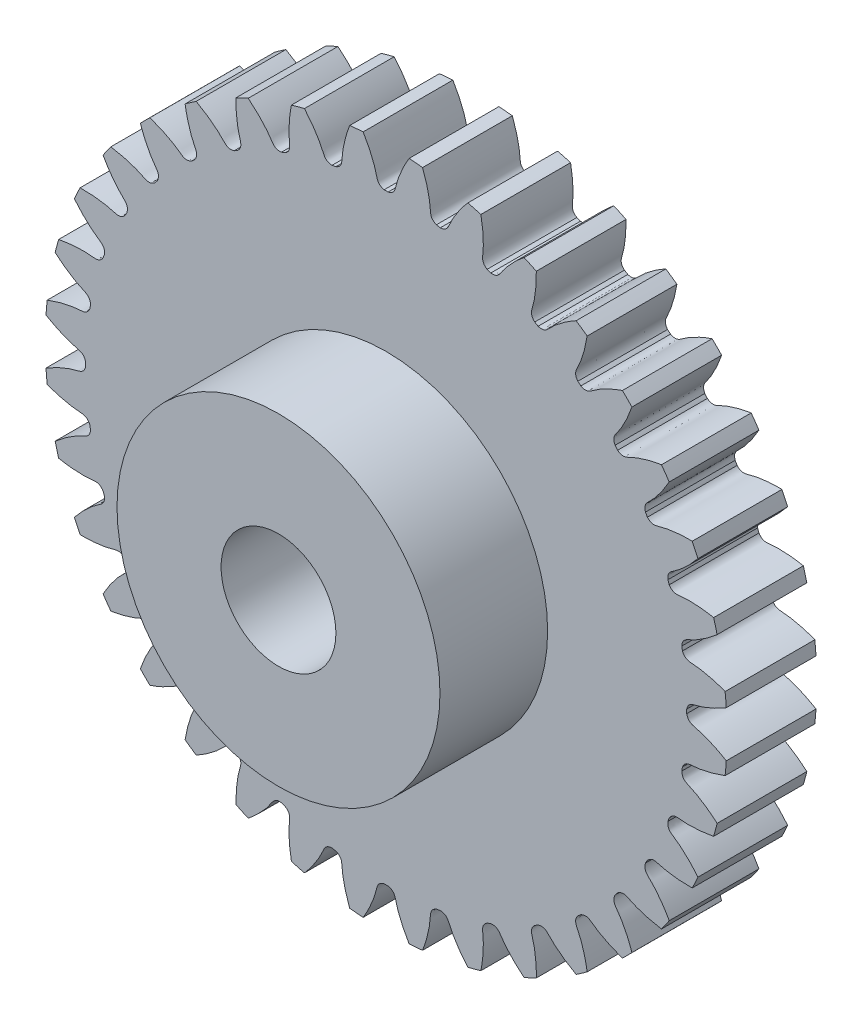
SolidWorks part; units mm, degrees
ref_plane "前视基准面" through (0, 0, 0) normal (0, 0, 1) x (1, 0, 0)
ref_plane "上视基准面" through (0, 0, 0) normal (0, 1, 0) x (1, 0, 0)
ref_plane "右视基准面" through (0, 0, 0) normal (1, 0, 0) x (0, 0, -1)
other "Configuration Table"
sketch "草图1" plane through (0, 0, 0) normal (0, 0, 1) x (1, 0, 0)
  circle A0 centre (0, 0) radius 9.5
extrude "凸台-拉伸1" add sketch "草图1" along normal blind 2.5
ref_axis "基准轴1" through (0, 0, 2.5) along (0, 0, -1)
sketch "草图2" plane through (0, 0, 0) normal (0, 0, 1) x (1, 0, 0)
  line L0 (0, 0) -> (0, 9.5) construction
  circle A0 centre (0, 0) radius 9.5 construction
  arc A1 (0.0549, 8.3748) -> (-0.0549, 8.3748) centre (0, 0) ccw
  arc A2 (1.757, 10.7884) -> (-1.757, 10.7884) centre (0, 0) ccw
  spline S0 degree 3 poles (0.0549, 8.3748) (0.235, 8.4152) (0.2505, 8.5493) (0.2882, 8.6914) (0.2997, 8.7319) (0.3131, 8.7753) (0.3284, 8.8217) (0.3457, 8.871) (0.3652, 8.9231) (0.3869, 8.9779) (0.4111, 9.0354) (0.4378, 9.0956) (0.4671, 9.1582) (0.4992, 9.2232) (0.5341, 9.2907) (0.5719, 9.3603) (0.6128, 9.4322) (0.6569, 9.5061) (0.7043, 9.582) (0.755, 9.6598) (0.8091, 9.7393) (0.8668, 9.8205) (0.9281, 9.9032) (0.9931, 9.9874) (1.0619, 10.0729) (1.1346, 10.1596) (1.2112, 10.2474) (1.2919, 10.3361) (1.3766, 10.4256) (1.4655, 10.5159) (1.5912, 10.6386) (1.6895, 10.7288) (1.757, 10.7884) knots 0 0 0 0 0.120371 0.133303 0.147364 0.162556 0.178878 0.19633 0.214913 0.234626 0.255469 0.277443 0.300547 0.324782 0.350146 0.376641 0.404267 0.433023 0.462909 0.493925 0.526072 0.559349 0.593757 0.629294 0.665963 0.703761 0.74269 0.782749 0.823939 0.866258 0.909709 1 1 1 1
  spline S1 degree 3 poles (-0.0549, 8.3748) (-0.235, 8.4152) (-0.2505, 8.5493) (-0.2882, 8.6914) (-0.2997, 8.7319) (-0.3131, 8.7753) (-0.3284, 8.8217) (-0.3457, 8.871) (-0.3652, 8.9231) (-0.3869, 8.9779) (-0.4111, 9.0354) (-0.4378, 9.0956) (-0.4671, 9.1582) (-0.4992, 9.2232) (-0.5341, 9.2907) (-0.5719, 9.3603) (-0.6128, 9.4322) (-0.6569, 9.5061) (-0.7043, 9.582) (-0.755, 9.6598) (-0.8091, 9.7393) (-0.8668, 9.8205) (-0.9281, 9.9032) (-0.9931, 9.9874) (-1.0619, 10.0729) (-1.1346, 10.1596) (-1.2112, 10.2474) (-1.2919, 10.3361) (-1.3766, 10.4256) (-1.4655, 10.5159) (-1.5912, 10.6386) (-1.6895, 10.7288) (-1.757, 10.7884) knots 0 0 0 0 0.120371 0.133303 0.147364 0.162556 0.178878 0.19633 0.214913 0.234626 0.255469 0.277443 0.300547 0.324782 0.350146 0.376641 0.404267 0.433023 0.462909 0.493925 0.526072 0.559349 0.593757 0.629294 0.665963 0.703761 0.74269 0.782749 0.823939 0.866258 0.909709 1 1 1 1
extrude "切除-拉伸1" cut sketch "草图2" along normal through all
pattern_circular "阵列(圆周)1" count 36 every 10 about axis through (0, 0, 2.5) along (0, 0, -1) of "切除-拉伸1"
sketch "草图3" plane through (0, 0, 0) normal (0, 0, 1) x (1, 0, 0)
  circle A0 centre (0, 0) radius 9 construction
  dimension "Dn" = 18
sketch "草图4" plane through (0, 0, 0) normal (0, 0, -1) x (-1, 0, 0)
  circle A0 centre (0, 0) radius 4.5
  dimension "D1" = 9
extrude "凸台-拉伸2" add sketch "草图4" against normal offset from surface (5.5 mm away) 3 up to face at (0, 0, 2.5) offset beyond the face yes
sketch "草图5" plane through (0, 0, 5.5) normal (0, 0, 1) x (1, 0, 0)
  circle A0 centre (0, 0) radius 1.6
  dimension "D1" = 3.2
extrude "切除-拉伸2" cut sketch "草图5" against normal up to next
